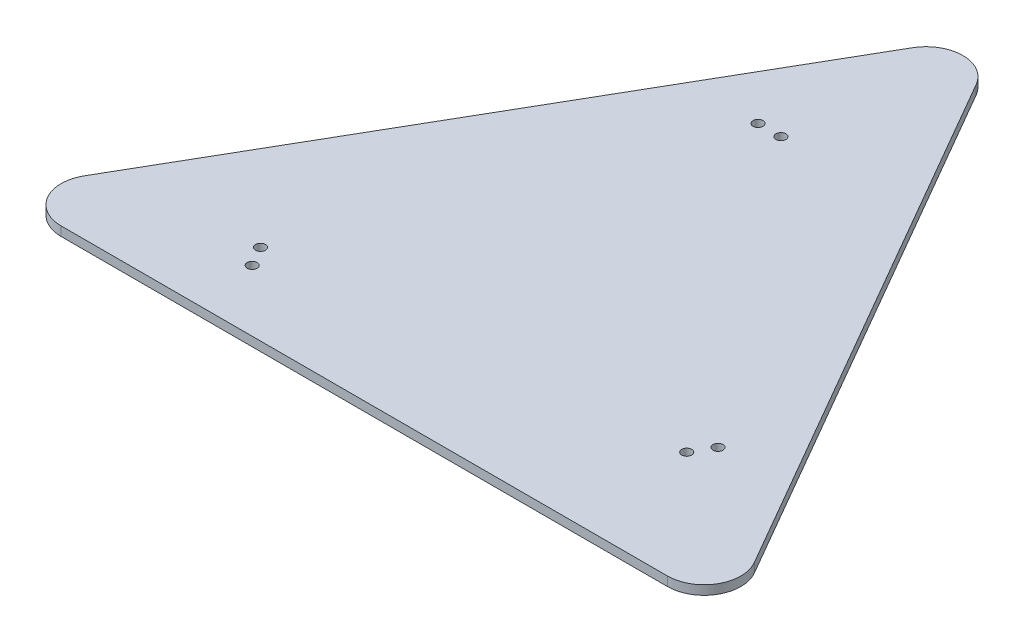
SolidWorks part; units mm, degrees
ref_plane "Front Plane" through (0, 0, 0) normal (0, 0, 1) x (1, 0, 0)
ref_plane "Top Plane" through (0, 0, 0) normal (0, 1, 0) x (1, 0, 0)
ref_plane "Right Plane" through (0, 0, 0) normal (1, 0, 0) x (0, 0, -1)
sketch "Sketch1" plane through (0, 0, 0) normal (0, 1, 0) x (1, 0, 0)
  line L1 (0, 146.647) -> (-127, -73.3235)
  line L2 (-127, -73.3235) -> (127, -73.3235)
  line L3 (127, -73.3235) -> (0, 146.647)
  circle A0 centre (0, 0) radius 73.3235 construction
  dimension "D1" = 254
extrude "Boss-Extrude1" add sketch "Sketch1" along normal blind 3.175
sketch "Sketch2" plane through (0, 3.175, 0) normal (0, 1, 0) x (1, 0, 0)
  line L0 (-127, -73.3235) -> (63.5, 36.6617) construction
  line L1 (127, -73.3235) -> (0, 146.647) construction
  line L2 (0, -73.3235) -> (0, 146.647) construction
  line L3 (-127, -73.3235) -> (127, -73.3235) construction
  line L5 (-63.5, 36.6617) -> (127, -73.3235) construction
  line L7 (0, 146.647) -> (-127, -73.3235) construction
  line L9 (0, -146.647) -> (127, 73.3235)
  line L11 (127, 73.3235) -> (-127, 73.3235)
  line L12 (-127, 73.3235) -> (0, -146.647)
  circle A0 centre (0, 0) radius 73.3235 construction
  line B0 (76.5144, -23.6451) -> (67.6244, -39.043) construction
  line B1 (72.39, -21.2638) -> (80.6389, -26.0263)
  line B2 (72.39, -21.2638) -> (63.5, -36.6617)
  line B3 (63.5, -36.6617) -> (71.7489, -41.4242)
  line B4 (80.6389, -26.0263) -> (71.7489, -41.4242)
  circle B5 centre (71.1931, -32.8618) radius 1.7272
  circle B6 centre (75.1555, -25.9987) radius 1.7272
  line B7 (-58.7344, -54.4409) -> (-67.6244, -39.043) construction
  line B8 (-54.61, -52.0597) -> (-62.8589, -56.8222)
  line B9 (-54.61, -52.0597) -> (-63.5, -36.6617)
  line B10 (-63.5, -36.6617) -> (-71.7489, -41.4242)
  line B11 (-62.8589, -56.8222) -> (-71.7489, -41.4242)
  circle B12 centre (-64.0557, -45.2242) radius 1.7272
  circle B13 centre (-60.0933, -52.0872) radius 1.7272
  line B14 (-17.78, 78.086) -> (0, 78.086) construction
  line B15 (-17.78, 73.3235) -> (-17.78, 82.8485)
  line B16 (-17.78, 73.3235) -> (0, 73.3235)
  line B17 (0, 73.3235) -> (0, 82.8485)
  line B18 (-17.78, 82.8485) -> (0, 82.8485)
  circle B19 centre (-7.1374, 78.086) radius 1.7272
  circle B20 centre (-15.0622, 78.086) radius 1.7272
  dimension "D1" = 254
sketch_block_instance "Block1-4"
sketch_block "Block1" parameters "D3"=3.4544, "D1"=17.78, "D2"=9.525, "D4"=7.1374, "D5"=7.9248
sketch_block_instance "Block1-5"
sketch_block_instance "Block1-6"
extrude "Cut-Extrude1" cut sketch "Sketch2" against normal through all contours B12 | B13 | B5 | B20 | B19 | B6 region at (71.1931, 3.175, 32.8618) region at (-64.0557, 3.175, 45.2242) region at (-60.0933, 3.175, 52.0872) region at (-7.1374, 3.175, -78.086) region at (-15.0622, 3.175, -78.086)
fillet "Fillet1" radius 12.7 3 edges at (127, 1.5875, 73.3235) (-127, 1.5875, 73.3235) (0, 1.5875, -146.647)
